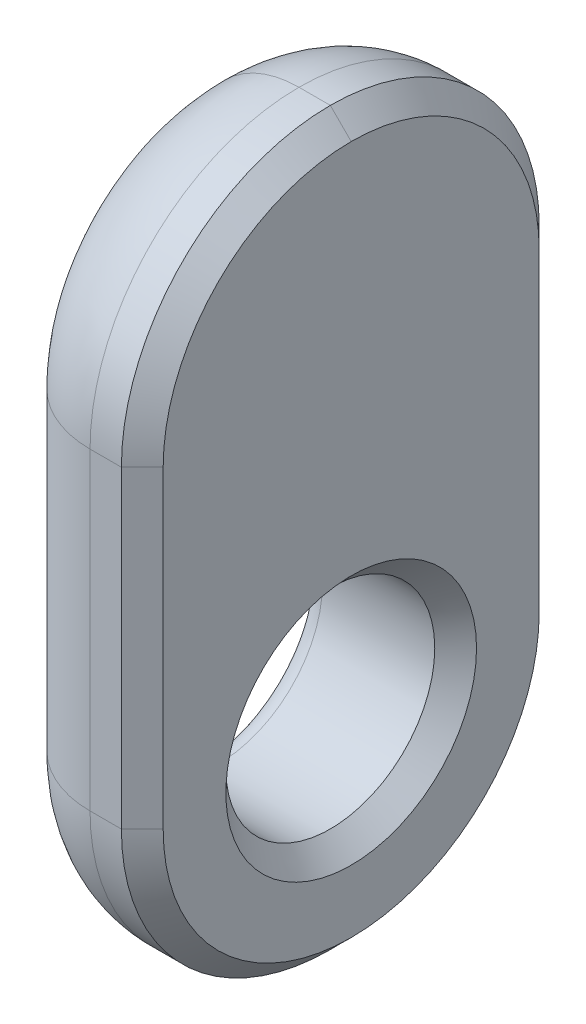
SolidWorks part; units mm, degrees
ref_plane "前视基准面" through (0, 0, 0) normal (0, 0, 1) x (1, 0, 0)
ref_plane "上视基准面" through (0, 0, 0) normal (0, 1, 0) x (1, 0, 0)
ref_plane "右视基准面" through (0, 0, 0) normal (1, 0, 0) x (0, 0, -1)
other "Configuration Table"
sketch "草图1" plane through (0, 0, 0) normal (1, 0, 0) x (0, 0, -1)
  circle A0 centre (0, 0) radius 2
  circle A1 centre (0, 0) radius 4
  dimension "D1" = 4
  dimension "D2" = 8
extrude "凸台-拉伸1" add sketch "草图1" along normal blind 3
sketch "草图2" plane through (3, 0, 0) normal (1, 0, 0) x (0, 0, -1)
  line L0 (2, 0) -> (4, 0)
  line L1 (-4, 0) -> (-2, 0)
  line L2 (-4, 0) -> (-4, 10)
  line L3 (-4, 10) -> (4, 10)
  line L4 (4, 0) -> (4, 10)
  circle A0 centre (0, 0) radius 4 construction
  arc A1 (2, 0) -> (-2, 0) centre (0, 0) ccw
  dimension "D1" = 10
extrude "凸台-拉伸2" add sketch "草图2" against normal blind 3
fillet "圆角1" radius 4 2 edges at (1.5, 10, -4) (1.5, 10, 4)
chamfer "倒角1" distance 0.4 angle 45 6 edges at (3, 0, -2) (3, -4, 0) (3, 3, 4) (3, 8.8284, 2.8284) (3, 8.8284, -2.8284) (3, 3, -4)
fillet "圆角2" radius 2 5 edges at (0, 3, 4) (0, 8.8284, 2.8284) (0, 8.8284, -2.8284) (0, 3, -4) (0, -4, 0)
fillet "圆角3" radius 0.4 2 edges at (0, 2, 0) (0, -2, 0)
